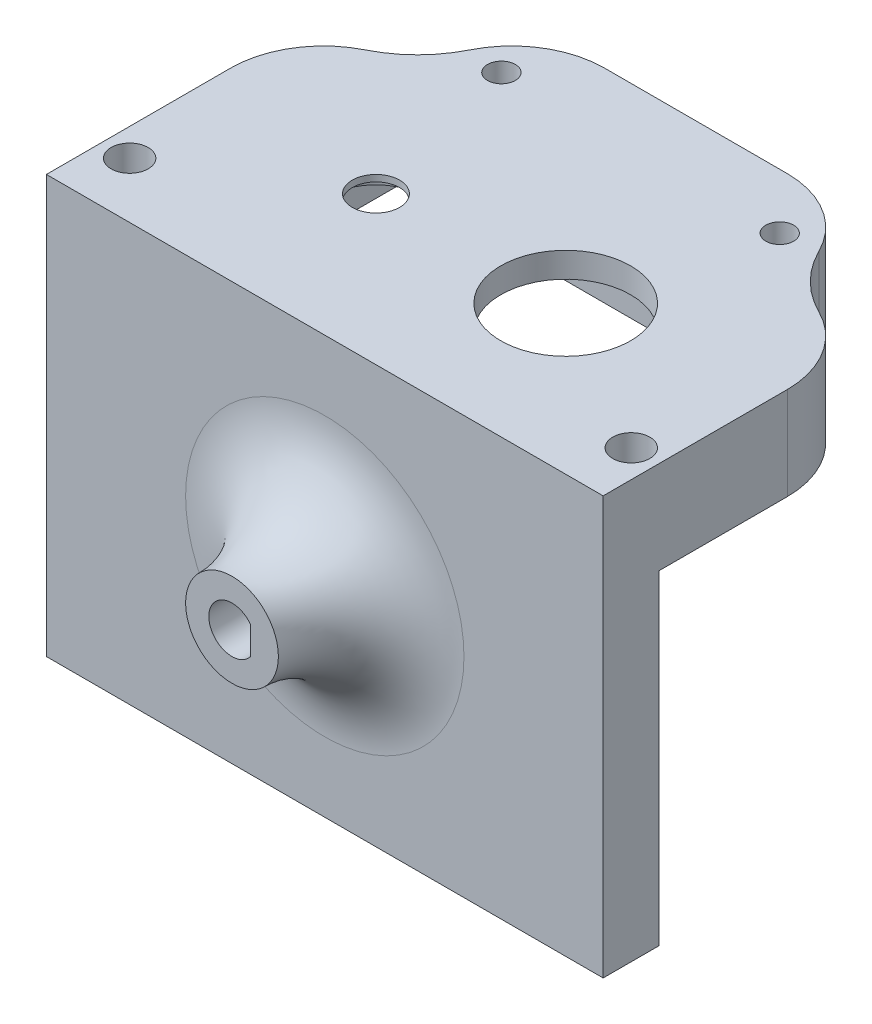
SolidWorks part; units mm, degrees
other "标注1"
sketch "草图3" plane through (-14.4573, 0, 19) normal (0, 0, 1) x (1, 0, 0)
ref_plane "前视基准面" through (0, 0, 0) normal (0, 0, 1) x (1, 0, 0)
ref_plane "上视基准面" through (0, 0, 0) normal (0, 1, 0) x (1, 0, 0)
ref_plane "右视基准面" through (0, 0, 0) normal (1, 0, 0) x (0, 0, -1)
other "Configuration Table"
sketch "草图4" plane through (0, 0, 0) normal (0, 1, 0) x (1, 0, 0)
  line L1 (30, -20) -> (-30, -20)
  line L2 (30, -20) -> (30, 20)
  line L3 (30, 20) -> (-30, 20)
  line L4 (-30, -20) -> (-30, 20)
  line L5 (30, -20) -> (-30, 20) construction
  line L6 (30, 20) -> (-30, -20) construction
  point P0 (0, 0)
extrude "凸台-拉伸2" add sketch "草图4" along normal blind 45
sketch "草图5" plane through (30, 0, 0) normal (1, 0, 0) x (0, 0, -1)
  line L1 (-20, 0) -> (20, 0) construction
  line L2 (-14, 0) -> (-14, 35)
  line L3 (-14, 35) -> (20, 35)
  line L4 (20, 45) -> (20, 0) construction
  line L5 (20, 35) -> (20, 0)
  line L6 (20, 0) -> (-14, 0)
  dimension "D1" = 35
extrude "切除-拉伸2" cut sketch "草图5" against normal through all
sketch "草图6" plane through (0, 35, 0) normal (0, -1, 0) x (1, 0, 0)
  line L2 (-24.25, 14) -> (-24.25, 7.936) construction
  line L3 (-30, 14) -> (30, 14) construction
  line L4 (-24.25, 7.936) -> (-30, 7.936) construction
  line L5 (-30, -20) -> (-30, 14) construction
  line L6 (-24.25, 7.936) -> (-24.25, -2.064) construction
  line L7 (0, 14) -> (0, -20) construction
  line L8 (-30, 14) -> (30, 14) construction
  line L9 (-30, -20) -> (30, -20) construction
  line L10 (24.25, 14) -> (24.25, 7.936) construction
  line L11 (24.25, 7.936) -> (30, 7.936) construction
  line L12 (24.25, 7.936) -> (24.25, -2.064) construction
  point P5 (-24.25, 7.936)
  point P8 (-24.25, -2.064)
  point P15 (24.25, 7.936)
  point P17 (24.25, -2.064)
  point P22 (-24.25, 7.936)
  point P24 (-24.25, -2.064)
  point P30 (24.25, 7.936)
  point P32 (24.25, -2.064)
  point P34 (24.25, -2.064)
  dimension "D1" = 5.75
hole_wizard "Ø3.0mm 暗销孔1" positions "草图6" profile "草图7" hole size "Ø3.0" standard "ISO"
sketch "草图7" plane through (24.25, 35, -2.064) normal (1, 0, 0) x (0, 0, -1)
  line L0 (0, 0) -> (0, 6.9013)
  line L1 (0, 6.9013) -> (1.5, 6)
  line L2 (1.5, 6) -> (1.5, 0)
  line L5 (1.5, 0) -> (0, 0)
  line L10 (0, 6.9013) -> (-1.5, 6) construction
  line L11 (0, -6.35) -> (0, 107.95) construction
  dimension "孔直径" = 3
  dimension "孔深度" = 6
  dimension "导头角度" = 118
sketch "草图8" plane through (0, 35, 0) normal (0, -1, 0) x (1, 0, 0)
  line L0 (-24.25, 7.936) -> (-20, 7.936) construction
  line L1 (-24.25, -2.064) -> (-20, -2.064) construction
  line L2 (-20, -2.064) -> (-20, 14)
  line L3 (-20, -2.064) -> (-20, -8.064)
  line L4 (-30, 14) -> (30, 14) construction
  line L5 (24.25, 7.936) -> (20, 7.936) construction
  line L6 (24.25, -2.064) -> (20, -2.064) construction
  line L7 (20, 14) -> (20, -8.064)
  line L8 (-20, -8.064) -> (20, -8.064)
  line L9 (-20, 14) -> (20, 14)
extrude "切除-拉伸3" cut sketch "草图8" against normal blind 7.3
sketch "草图9" plane through (0, 42.3, 0) normal (0, -1, 0) x (1, 0, 0)
  circle A0 centre (10.009, 4.0471) radius 7
extrude "切除-拉伸4" cut sketch "草图9" against normal blind 8.3
sketch "草图10" plane through (0, 42.3, 0) normal (0, -1, 0) x (1, 0, 0)
  line L0 (17.009, 4.0471) -> (-12.991, 4.0471) construction
  circle A0 centre (10.009, 4.0471) radius 7 construction
  circle A1 centre (-10.4401, 4.0471) radius 2.5508
  dimension "D1" = 30
extrude "切除-拉伸5" cut sketch "草图10" against normal blind 8.3
sketch "草图11" plane through (0, 42.3, 0) normal (0, -1, 0) x (1, 0, 0)
  circle A0 centre (-10.4401, 4.0471) radius 5
extrude "切除-拉伸6" cut sketch "草图11" against normal blind 2
sketch "草图13" plane through (0, 35, 0) normal (0, -1, 0) x (1, 0, 0)
  line L0 (-20, 4.3953) -> (-27, 4.3953)
  line L1 (-20, 14) -> (-20, -8.064) construction
  line L2 (-27, 4.3953) -> (-27, 2.8953)
  line L3 (-27, 2.8953) -> (-20, 2.968)
  line L4 (-20, 14) -> (-20, -8.064) construction
  line L5 (-20, 2.968) -> (-20, 4.3953)
  line L6 (0, 20) -> (0, -20) construction
  line L7 (-30, 20) -> (30, 20) construction
  line L8 (-30, -20) -> (30, -20) construction
  line L9 (20, 2.968) -> (20, 4.3953)
  line L10 (27, 2.8953) -> (20, 2.968)
  line L11 (27, 4.3953) -> (27, 2.8953)
  line L12 (20, 4.3953) -> (27, 4.3953)
extrude "切除-拉伸7" cut sketch "草图13" against normal blind 3
sketch "草图14" plane through (0, 0, 14) normal (0, 0, -1) x (-1, 0, 0)
  line L0 (30, 35) -> (30, 0) construction
  line L2 (-25.2836, 9.4448) -> (27, 9.4448)
  line L3 (27, 9.4448) -> (27, 4.0051)
  line L4 (27, 4.0051) -> (-25.2836, 4.0051)
  line L5 (-25.2836, 4.0051) -> (-25.2836, 9.4448)
  dimension "D1" = 3
extrude "切除-拉伸8" cut sketch "草图14" against normal blind 3
sketch "草图15" plane through (0, 0, 20) normal (0, 0, 1) x (1, 0, 0)
  line L0 (0, 45) -> (0, 0) construction
  line L1 (-30, 45) -> (30, 45) construction
  line L2 (-30, 22.5) -> (0, 22.5) construction
  line L3 (-30, 45) -> (-30, 0) construction
  line L4 (0, 22.5) -> (30, 22.5) construction
  line L5 (30, 45) -> (30, 0) construction
  line L6 (2, 24) -> (2, 21)
  circle A0 centre (0, 22.5) radius 5
  arc A1 (2, 24) -> (2, 21) centre (0, 22.5) ccw
  point P17 (-2.5, 22.5)
  dimension "D1" = 4.5
extrude "凸台-拉伸3" add sketch "草图15" along normal blind 10
fillet "圆角1" radius 10 1 edges at (-5, 22.5, 20)
sketch "草图16" plane through (0, 35, 0) normal (0, -1, 0) x (1, 0, 0)
  line L0 (0, -20) -> (0, -8.064) construction
  line L1 (-30, -20) -> (30, -20) construction
  line L2 (-20, -8.064) -> (20, -8.064) construction
  line L3 (0, -14.032) -> (-30, -14.032) construction
  line L4 (-30, -20) -> (-30, 14) construction
  line L5 (0, -14.032) -> (30, -14.032) construction
  line L6 (30, -20) -> (30, 14) construction
  point P15 (-15, -14.032)
  point P17 (15, -14.032)
hole_wizard "Ø3.0mm 暗销孔2" positions "草图16" profile "草图17" hole size "Ø3.0" standard "ISO" end condition through all
sketch "草图17" plane through (15, 35, -14.032) normal (1, 0, 0) x (0, 0, -1)
  line L0 (0, 0) -> (0, 10)
  line L1 (0, 10) -> (1.5, 10)
  line L2 (1.5, 10) -> (1.5, 0)
  line L5 (1.5, 0) -> (0, 0)
  line L11 (0, -6.35) -> (0, 107.95) construction
  dimension "通孔孔直径" = 3
  dimension "通孔孔深度" = 10
sketch "草图18" plane through (0, 45, 0) normal (0, 1, 0) x (1, 0, 0)
  line L0 (-30.032, -14) -> (-27.032, -14) construction
  line L2 (-27.032, -14) -> (-27.032, -20) construction
  line L3 (-30, -20) -> (30, -20) construction
  line L4 (0, 20) -> (0, -20) construction
  line L5 (30, 20) -> (-30, 20) construction
  line L6 (-15, -20) -> (15, -20) construction
  circle A0 centre (-27.032, -14) radius 2
  circle A1 centre (27.032, -14) radius 2
  dimension "D1" = 3
  dimension "D2" = 6
extrude "切除-拉伸9" cut sketch "草图18" against normal blind 8
sketch "草图20" plane through (0, 35, 0) normal (0, -1, 0) x (1, 0, 0)
  line L0 (-30, -7.5) -> (-30, -20)
  line L1 (-30, -20) -> (-17.5, -20)
  line L2 (0, 14) -> (0, -20) construction
  line L3 (-30, 14) -> (30, 14) construction
  line L4 (-30, -20) -> (30, -20) construction
  line L5 (30, -20) -> (17.5, -20)
  line L6 (30, -7.5) -> (30, -20)
  arc A0 (-17.5, -20) -> (-30, -7.5) centre (-30, -20) ccw
  arc A1 (17.5, -20) -> (30, -7.5) centre (30, -20) cw
extrude "切除-拉伸10" cut sketch "草图20" against normal blind 10
fillet "圆角2" radius 10 4 edges at (30, 40, -7.5) (17.5, 40, -20) (-30, 40, -7.5) (-17.5, 40, -20)
